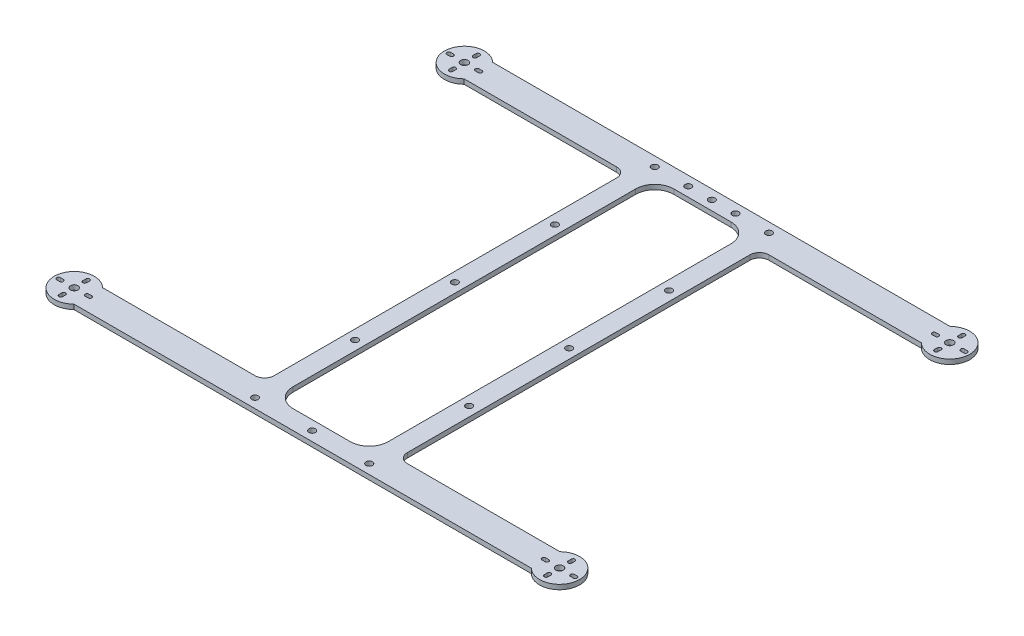
SolidWorks part; units mm, degrees
ref_plane "Front Plane" through (0, 0, 0) normal (0, 0, 1) x (1, 0, 0)
ref_plane "Top Plane" through (0, 0, 0) normal (0, 1, 0) x (1, 0, 0)
ref_plane "Right Plane" through (0, 0, 0) normal (1, 0, 0) x (0, 0, -1)
sketch "Sketch1" plane through (0, 0, 0) normal (0, 1, 0) x (1, 0, 0)
  line L1 (-44.45, 139.7) -> (44.45, 139.7)
  line L2 (-44.45, 120.65) -> (-44.45, -120.65)
  line L3 (-44.45, -139.7) -> (44.45, -139.7)
  line L4 (44.45, 120.65) -> (44.45, -120.65)
  line L5 (44.45, 139.7) -> (161.925, 139.7)
  line L7 (44.45, 120.65) -> (161.925, 120.65)
  line L8 (161.925, 139.7) -> (161.925, 120.65)
  line L14 (0, 0) -> (0, 187.5455) construction
  line L17 (0, 0) -> (-239.6804, 0) construction
  line L21 (0, 0) -> (44.45, 0) construction
  line L22 (-44.45, 120.65) -> (-161.925, 120.65)
  line L23 (-44.45, 139.7) -> (-161.925, 139.7)
  line L24 (-161.925, 139.7) -> (-161.925, 120.65)
  line L37 (-31.75, 127) -> (31.75, 127)
  line L40 (-31.75, 127) -> (-31.75, -127)
  line L43 (-31.75, -127) -> (31.75, -127)
  line L46 (31.75, 127) -> (31.75, -127)
  line L49 (44.45, -120.65) -> (161.925, -120.65)
  line L50 (44.45, -139.7) -> (161.925, -139.7)
  line L51 (161.925, -139.7) -> (161.925, -120.65)
  line L88 (-161.925, -139.7) -> (-161.925, -120.65)
  line L89 (-44.45, -139.7) -> (-161.925, -139.7)
  line L90 (-44.45, -120.65) -> (-161.925, -120.65)
  point P4 (0, 139.7)
  point P6 (-44.45, 0)
  dimension "D4" = 117.475
  dimension "D1" = 279.4
  dimension "D2" = 88.9
  dimension "D3" = 19.05
  dimension "D6" = 12.7
  dimension "D7" = 12.7
  dimension "D8" = 12.7
  dimension "D10" = 117.475
  dimension "D12" = 12.7
  dimension "D18" = 19.05
extrude "Boss-Extrude1" add sketch "Sketch1" along normal blind 3.175
sketch "Sketch4" plane through (0, 3.175, 0) normal (0, 1, 0) x (1, 0, 0)
  line L0 (161.925, 120.65) -> (161.925, 139.7) construction
  line L1 (-161.925, 139.7) -> (-161.925, 120.65) construction
  line L2 (-161.925, -120.65) -> (-161.925, -139.7) construction
  line L3 (161.925, -139.7) -> (161.925, -120.65) construction
  circle A0 centre (161.925, 130.175) radius 13.335
  circle A1 centre (-161.925, 130.175) radius 13.335
  circle A2 centre (-161.925, -130.175) radius 13.335
  circle A3 centre (161.925, -130.175) radius 13.335
  point P18 (161.925, -130.175)
extrude "Boss-Extrude4" add sketch "Sketch4" against normal up to surface (3.175 mm away) up to face at (0, 0, 0)
sketch "Sketch5" plane through (0, 3.175, 0) normal (0, 1, 0) x (1, 0, 0)
  line L0 (151.425, 130.175) -> (153.425, 130.175) construction
  line L1 (151.425, 131.425) -> (153.425, 131.425)
  line L2 (151.425, 128.925) -> (153.425, 128.925)
  line L3 (161.925, 130.175) -> (161.925, 143.51) construction
  line L4 (172.425, 130.175) -> (170.425, 130.175) construction
  line L5 (172.425, 131.425) -> (170.425, 131.425)
  line L6 (172.425, 128.925) -> (170.425, 128.925)
  line L7 (161.925, 139.175) -> (161.925, 137.175) construction
  line L8 (163.175, 139.175) -> (163.175, 137.175)
  line L9 (160.675, 139.175) -> (160.675, 137.175)
  line L10 (161.925, 130.175) -> (175.26, 130.175) construction
  line L11 (161.925, 121.175) -> (161.925, 123.175) construction
  line L12 (163.175, 121.175) -> (163.175, 123.175)
  line L13 (160.675, 121.175) -> (160.675, 123.175)
  line L14 (0, 0) -> (0, 263.0018) construction
  line L15 (0, 0) -> (558.7896, 0) construction
  line L16 (-151.425, 130.175) -> (-153.425, 130.175) construction
  line L17 (-151.425, 131.425) -> (-153.425, 131.425)
  line L18 (-151.425, 128.925) -> (-153.425, 128.925)
  line L19 (-172.425, 130.175) -> (-170.425, 130.175) construction
  line L20 (-172.425, 131.425) -> (-170.425, 131.425)
  line L21 (-172.425, 128.925) -> (-170.425, 128.925)
  line L22 (-161.925, 139.175) -> (-161.925, 137.175) construction
  line L23 (-163.175, 139.175) -> (-163.175, 137.175)
  line L24 (-160.675, 139.175) -> (-160.675, 137.175)
  line L25 (-161.925, 121.175) -> (-161.925, 123.175) construction
  line L26 (-163.175, 121.175) -> (-163.175, 123.175)
  line L27 (-160.675, 121.175) -> (-160.675, 123.175)
  line L28 (-161.925, 130.175) -> (-175.26, 130.175) construction
  line L29 (-161.925, 130.175) -> (-161.925, 143.51) construction
  line L30 (151.425, -130.175) -> (153.425, -130.175) construction
  line L31 (151.425, -131.425) -> (153.425, -131.425)
  line L32 (151.425, -128.925) -> (153.425, -128.925)
  line L33 (161.925, -139.175) -> (161.925, -137.175) construction
  line L34 (163.175, -139.175) -> (163.175, -137.175)
  line L35 (160.675, -139.175) -> (160.675, -137.175)
  line L36 (172.425, -130.175) -> (170.425, -130.175) construction
  line L37 (172.425, -131.425) -> (170.425, -131.425)
  line L38 (172.425, -128.925) -> (170.425, -128.925)
  line L39 (161.925, -121.175) -> (161.925, -123.175) construction
  line L40 (163.175, -121.175) -> (163.175, -123.175)
  line L41 (160.675, -121.175) -> (160.675, -123.175)
  line L42 (161.925, -130.175) -> (175.26, -130.175) construction
  line L43 (161.925, -130.175) -> (161.925, -143.51) construction
  line L44 (-161.925, -130.175) -> (-161.925, -143.51) construction
  line L45 (-161.925, -130.175) -> (-175.26, -130.175) construction
  line L46 (-161.925, -121.175) -> (-161.925, -123.175) construction
  line L47 (-163.175, -121.175) -> (-163.175, -123.175)
  line L48 (-160.675, -121.175) -> (-160.675, -123.175)
  line L49 (-161.925, -139.175) -> (-161.925, -137.175) construction
  line L50 (-163.175, -139.175) -> (-163.175, -137.175)
  line L51 (-160.675, -139.175) -> (-160.675, -137.175)
  line L52 (-172.425, -130.175) -> (-170.425, -130.175) construction
  line L53 (-172.425, -131.425) -> (-170.425, -131.425)
  line L54 (-172.425, -128.925) -> (-170.425, -128.925)
  line L55 (-151.425, -130.175) -> (-153.425, -130.175) construction
  line L56 (-151.425, -131.425) -> (-153.425, -131.425)
  line L57 (-151.425, -128.925) -> (-153.425, -128.925)
  circle A0 centre (161.925, 130.175) radius 2.5
  arc A1 (151.425, 131.425) -> (151.425, 128.925) centre (151.425, 130.175) ccw
  arc A2 (153.425, 128.925) -> (153.425, 131.425) centre (153.425, 130.175) ccw
  arc A3 (152.5924, 120.65) -> (152.5924, 139.7) centre (161.925, 130.175) ccw construction
  arc A4 (172.425, 131.425) -> (172.425, 128.925) centre (172.425, 130.175) cw
  arc A5 (170.425, 128.925) -> (170.425, 131.425) centre (170.425, 130.175) cw
  arc A6 (163.175, 139.175) -> (160.675, 139.175) centre (161.925, 139.175) ccw
  arc A7 (160.675, 137.175) -> (163.175, 137.175) centre (161.925, 137.175) ccw
  arc A8 (163.175, 121.175) -> (160.675, 121.175) centre (161.925, 121.175) cw
  arc A9 (160.675, 123.175) -> (163.175, 123.175) centre (161.925, 123.175) cw
  arc A10 (-151.425, 131.425) -> (-151.425, 128.925) centre (-151.425, 130.175) cw
  arc A11 (-153.425, 128.925) -> (-153.425, 131.425) centre (-153.425, 130.175) cw
  arc A12 (-172.425, 131.425) -> (-172.425, 128.925) centre (-172.425, 130.175) ccw
  arc A13 (-170.425, 128.925) -> (-170.425, 131.425) centre (-170.425, 130.175) ccw
  arc A14 (-163.175, 139.175) -> (-160.675, 139.175) centre (-161.925, 139.175) cw
  arc A15 (-160.675, 137.175) -> (-163.175, 137.175) centre (-161.925, 137.175) cw
  arc A16 (-163.175, 121.175) -> (-160.675, 121.175) centre (-161.925, 121.175) ccw
  arc A17 (-160.675, 123.175) -> (-163.175, 123.175) centre (-161.925, 123.175) ccw
  circle A18 centre (-161.925, 130.175) radius 2.5
  arc A19 (151.425, -131.425) -> (151.425, -128.925) centre (151.425, -130.175) cw
  arc A20 (153.425, -128.925) -> (153.425, -131.425) centre (153.425, -130.175) cw
  arc A21 (163.175, -139.175) -> (160.675, -139.175) centre (161.925, -139.175) cw
  arc A22 (160.675, -137.175) -> (163.175, -137.175) centre (161.925, -137.175) cw
  arc A23 (172.425, -131.425) -> (172.425, -128.925) centre (172.425, -130.175) ccw
  arc A24 (170.425, -128.925) -> (170.425, -131.425) centre (170.425, -130.175) ccw
  arc A25 (163.175, -121.175) -> (160.675, -121.175) centre (161.925, -121.175) ccw
  arc A26 (160.675, -123.175) -> (163.175, -123.175) centre (161.925, -123.175) ccw
  circle A27 centre (161.925, -130.175) radius 2.5
  circle A28 centre (-161.925, -130.175) radius 2.5
  arc A29 (-163.175, -121.175) -> (-160.675, -121.175) centre (-161.925, -121.175) cw
  arc A30 (-160.675, -123.175) -> (-163.175, -123.175) centre (-161.925, -123.175) cw
  arc A31 (-163.175, -139.175) -> (-160.675, -139.175) centre (-161.925, -139.175) ccw
  arc A32 (-160.675, -137.175) -> (-163.175, -137.175) centre (-161.925, -137.175) ccw
  arc A33 (-172.425, -131.425) -> (-172.425, -128.925) centre (-172.425, -130.175) cw
  arc A34 (-170.425, -128.925) -> (-170.425, -131.425) centre (-170.425, -130.175) cw
  arc A35 (-151.425, -131.425) -> (-151.425, -128.925) centre (-151.425, -130.175) ccw
  arc A36 (-153.425, -128.925) -> (-153.425, -131.425) centre (-153.425, -130.175) ccw
  point P5 (152.425, 130.175)
  point P16 (171.425, 130.175)
  point P23 (161.925, 138.175)
  point P31 (161.925, 122.175)
  point P42 (-152.425, 130.175)
  point P49 (-171.425, 130.175)
  point P56 (-161.925, 138.175)
  point P63 (-161.925, 122.175)
  point P74 (152.425, -130.175)
  point P81 (161.925, -138.175)
  point P88 (171.425, -130.175)
  point P95 (161.925, -122.175)
  point P110 (-161.925, -122.175)
  point P117 (-161.925, -138.175)
  point P124 (-171.425, -130.175)
  point P131 (-152.425, -130.175)
  dimension "D1" = 5
  dimension "D2" = 2.5
  dimension "D3" = 2
  dimension "D4" = 19
  dimension "D5" = 2.5
  dimension "D6" = 2
  dimension "D7" = 16
extrude "Motor Holes" cut sketch "Sketch5" against normal through all
sketch "Sketch7" plane through (0, 3.175, 0) normal (0, 1, 0) x (1, 0, 0)
  line L0 (152.5924, 139.7) -> (-152.5924, 139.7) construction
  line L1 (-44.45, 120.65) -> (-44.45, -120.65) construction
  line L2 (0, 0) -> (0, 246.0772) construction
  line L3 (0, 0) -> (301.4392, 0) construction
  circle A0 centre (-38.1, 133.35) radius 2.159
  circle A1 centre (-38.1, 66.675) radius 2.159
  circle A2 centre (-38.1, 0) radius 2.159
  circle A3 centre (-38.1, -66.675) radius 2.159
  circle A5 centre (-38.1, -133.35) radius 2.159
  circle A6 centre (38.1, -133.35) radius 2.159
  circle A7 centre (38.1, -66.675) radius 2.159
  circle A8 centre (38.1, 0) radius 2.159
  circle A9 centre (38.1, 66.675) radius 2.159
  circle A10 centre (38.1, 133.35) radius 2.159
  circle A11 centre (0, 133.35) radius 2.159
  circle A12 centre (0, -133.35) radius 2.159
  dimension "D1" = 4.318
  dimension "D2" = 6.35
  dimension "D3" = 6.35
  dimension "D4" = 66.675
  dimension "D5" = 66.675
  dimension "D6" = 66.675
  dimension "D7" = 66.675
extrude "Cut-Extrude2" cut sketch "Sketch7" against normal through all
fillet "Fillet1" radius 12.7 4 edges at (31.75, 1.5875, 127) (-31.75, 1.5875, 127) (-31.75, 1.5875, -127) (31.75, 1.5875, -127)
fillet "Fillet2" radius 6.35 4 edges at (-44.45, 1.5875, 120.65) (-44.45, 1.5875, -120.65) (44.45, 1.5875, -120.65) (44.45, 1.5875, 120.65)
sketch "Sketch8" plane through (0, 3.175, 0) normal (0, 1, 0) x (1, 0, 0)
  line L0 (152.5924, 139.7) -> (-152.5924, 139.7) construction
  line L1 (0, 139.7) -> (0, 110.7046) construction
  circle A0 centre (-15.7442, 133.35) radius 2.159
  circle A1 centre (15.7442, 133.35) radius 2.159
  dimension "D5" = 4.318
  dimension "D6" = 4.318
  dimension "D1" = 6.35
  dimension "D2" = 6.35
  dimension "D3" = 31.4884
  dimension "D4" = 15.7442
extrude "Cut-Extrude3" cut sketch "Sketch8" against normal blind 12.7
